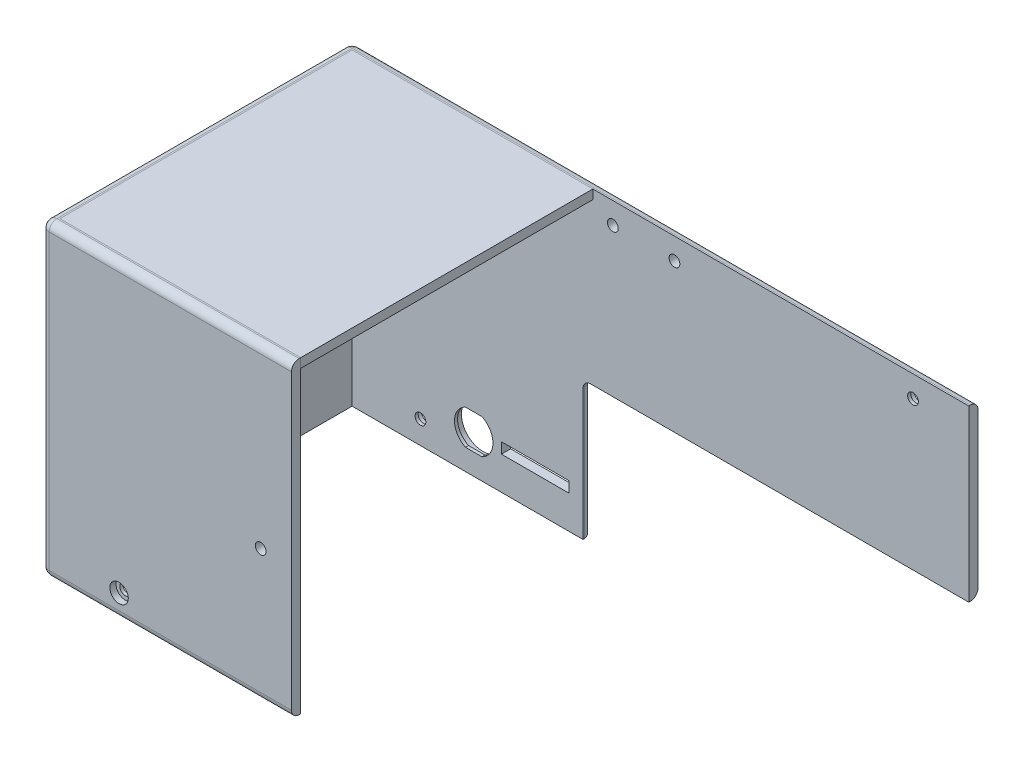
SolidWorks part; units mm, degrees
ref_plane "Front Plane" through (0, 0, 0) normal (0, 0, 1) x (1, 0, 0)
ref_plane "Top Plane" through (0, 0, 0) normal (0, 1, 0) x (1, 0, 0)
ref_plane "Right Plane" through (0, 0, 0) normal (1, 0, 0) x (0, 0, -1)
sketch "Sketch1" plane through (0, 0, 0) normal (0, 1, 0) x (1, 0, 0)
  line L0 (0, 0) -> (203.3, 0)
  line L1 (203.3, 0) -> (203.3, -3)
  line L2 (203.3, -3) -> (3, -3)
  line L5 (0, -100.9) -> (0, 0)
  line L9 (81.2, -100.9) -> (81.2, -97.9)
  line L11 (81.2, -97.9) -> (3, -97.9)
  line L12 (3, -97.9) -> (3, -3)
  line L13 (0, -100.9) -> (81.2, -100.9)
  dimension "D1" = 200.3
  dimension "D2" = 3
  dimension "D3" = 81.2
  dimension "D4" = 3
  dimension "D5" = 100.9
  dimension "D6" = 3
extrude "Main_Body" add sketch "Sketch1" along normal blind 100.2
sketch "Sketch3" plane through (0, 0, 0) normal (-1, 0, 0) x (0, 0, 1)
  line L0 (0, 0) -> (100.9, 0) construction
  line L1 (0, 100.2) -> (0, 0) construction
  line L2 (17.5, 7.5) -> (83.4, 7.5) construction
  line L3 (100.9, 100.2) -> (100.9, 0) construction
  circle A0 centre (83.4, 7.5) radius 1.75
  circle A1 centre (17.5, 7.5) radius 1.75
  dimension "D1" = 3.5
  dimension "D3" = 3.5
  dimension "D2" = 7.5
  dimension "D4" = 17.5
  dimension "D5" = 17.5
extrude "Left_Screw_Holes" [suppressed] cut sketch "Sketch3" against normal blind 10
sketch "Sketch4" [suppressed] plane through (0, 0, 0) normal (-1, 0, 0) x (0, 0, 1)
  circle A0 centre (17.5, 7.5) radius 3
  circle A1 centre (83.4, 7.5) radius 3
  dimension "D1" = 6
  dimension "D2" = 6
extrude "Left_Screw_Heads" [suppressed] cut sketch "Sketch4" against normal blind 2
sketch "Sketch5" plane through (0, 0, 0) normal (0, 0, -1) x (-1, 0, 0)
  line L0 (0, 100.2) -> (0, 0) construction
  line L1 (-203.3, 0) -> (0, 0) construction
  line L2 (-25.2, 7.5) -> (-185.2, 7.5) construction
  line L3 (-185.2, 7.5) -> (-185.2, 93.2) construction
  line L4 (-185.2, 93.2) -> (-185.2, 100.2) construction
  line L5 (-203.3, 100.2) -> (0, 100.2) construction
  circle A0 centre (-25.2, 7.5) radius 1.75
  circle A1 centre (-185.2, 7.5) radius 1.75
  circle A2 centre (-185.2, 93.2) radius 1.75
  dimension "D1" = 3.5
  dimension "D2" = 25.2
  dimension "D3" = 7.5
  dimension "D5" = 3.5
  dimension "D6" = 3.5
  dimension "D4" = 160
  dimension "D7" = 7
extrude "Back_Screw_Holes" cut sketch "Sketch5" against normal blind 10
sketch "Sketch12" plane through (0, 0, 0) normal (0, 0, -1) x (-1, 0, 0)
  circle A0 centre (-25.2, 7.5) radius 3
  circle A1 centre (-185.2, 7.5) radius 3
  circle A2 centre (-185.2, 93.2) radius 3
  dimension "D1" = 6
  dimension "D2" = 6
  dimension "D3" = 6
extrude "Back_Screw_Heads" cut sketch "Sketch12" against normal blind 2
sketch "Sketch6" plane through (0, 0, 3) normal (0, 0, 1) x (1, 0, 0)
  line L1 (78, 45) -> (298, 45)
  line L2 (78, 45) -> (78, 0)
  line L3 (78, 0) -> (298, 0)
  line L4 (298, 45) -> (298, 0)
  line L5 (3, 0) -> (203.3, 0) construction
  line L6 (0, 100.2) -> (0, 0) construction
  dimension "D1" = 45
  dimension "D2" = 220
  dimension "D4" = 78
extrude "Paper_Through_Hole" cut sketch "Sketch6" against normal blind 10
sketch "Sketch7" plane through (0, 0, 100.9) normal (0, 0, 1) x (1, 0, 0)
  line L0 (0, 0) -> (81.2, 0) construction
  line L1 (0, 100.2) -> (0, 0) construction
  circle A0 centre (25.2, 7.5) radius 1.75
  dimension "D1" = 3.5
  dimension "D2" = 7.5
  dimension "D3" = 25.2
extrude "Front_Left_Screw_Hole" cut sketch "Sketch7" against normal blind 10
sketch "Sketch8" plane through (0, 0, 100.9) normal (0, 0, 1) x (1, 0, 0)
  circle A0 centre (25.2, 7.5) radius 3
  dimension "D1" = 6
extrude "Front_Left_Screw_Head" cut sketch "Sketch8" against normal blind 2
sketch "Sketch9" plane through (0, 100.2, 0) normal (0, 1, 0) x (1, 0, 0)
  line L1 (81.2, -97.9) -> (3, -97.9)
  line L2 (81.2, -97.9) -> (81.2, -3)
  line L3 (81.2, -3) -> (3, -3)
  line L4 (3, -97.9) -> (3, -3)
extrude "Boss-Extrude1" add sketch "Sketch9" against normal blind 3 separate body
sketch "Sketch10" plane through (0, 0, 0) normal (0, 0, -1) x (-1, 0, 0)
  line L0 (-107.7, 93.2) -> (-87.7, 93.2) construction
  line L1 (-203.3, 100.2) -> (0, 100.2) construction
  line L2 (0, 93.2) -> (-87.7, 93.2) construction
  line L3 (0, 100.2) -> (0, 0) construction
  circle A0 centre (-107.7, 93.2) radius 1.75
  circle A1 centre (-87.7, 93.2) radius 1.75
  dimension "D1" = 20
  dimension "D3" = 3.5
  dimension "D4" = 3.5
  dimension "D2" = 7
  dimension "D5" = 87.7
extrude "Hinge_Holes" cut sketch "Sketch10" against normal blind 10
sketch "Sketch11" plane through (0, 0, 100.9) normal (0, 0, 1) x (1, 0, 0)
  line L0 (0, 0) -> (81.2, 0) construction
  line L1 (81.2, 100.2) -> (81.2, 0) construction
  circle A0 centre (71.2, 43) radius 1.75
  dimension "D1" = 43
  dimension "D3" = 3.5
  dimension "D2" = 10
extrude "Latch_Hole" cut sketch "Sketch11" against normal blind 10
fillet "Fillet3" radius 2.5 11 edges at (101.65, 100.2, 0) (0, 100.2, 50.45) (0, 50.1, 0) (0, 50.1, 100.9) (40.6, 0, 100.9) (39, 0, 0) (0, 0, 50.45) (40.6, 100.2, 100.9) (140.65, 45, 0) (78, 45, 1.5) (78, 22.5, 0)
sketch "Sketch13" plane through (0, 0, 0) normal (0, 0, -1) x (-1, 0, 0)
  line L0 (-75.5, 2.5) -> (-2.5, 2.5) construction
  line L1 (-2.5, 2.5) -> (-2.5, 97.7) construction
  circle A0 centre (-42.5, 12.5) radius 7
  dimension "D1" = 14
  dimension "D2" = 10
  dimension "D3" = 40
extrude "Cut-Extrude1" cut sketch "Sketch13" against normal blind 2
sketch "Sketch14" plane through (0, 0, 2) normal (0, 0, -1) x (-1, 0, 0)
  line L0 (-45.1721, 18.15) -> (-39.8279, 18.15)
  line L1 (-39.8279, 6.85) -> (-45.1721, 6.85)
  arc A0 (-39.8279, 18.15) -> (-39.8279, 6.85) centre (-42.5, 12.5) cw
  arc A1 (-45.1721, 6.85) -> (-45.1721, 18.15) centre (-42.5, 12.5) cw
  circle A2 centre (-42.5, 12.5) radius 7 construction
  dimension "D1" = 6.25
  dimension "D3" = 6.25
  dimension "D2" = 11.3
extrude "Cut-Extrude2" cut sketch "Sketch14" against normal up to next (1 mm away)
sketch "Sketch15" plane through (0, 0, 0) normal (0, 0, -1) x (-1, 0, 0)
  line L0 (-49.5, 12.5) -> (-51.5, 12.5) construction
  line L1 (-73.5, 14.25) -> (-51.5, 14.25)
  line L2 (-73.5, 14.25) -> (-73.5, 10.75)
  line L3 (-73.5, 10.75) -> (-51.5, 10.75)
  line L4 (-51.5, 14.25) -> (-51.5, 10.75)
  line L5 (-73.5, 12.5) -> (-75.5, 12.5) construction
  line L6 (-75.5, 42.5) -> (-75.5, 2.5) construction
  circle A0 centre (-42.5, 12.5) radius 7 construction
  circle A1 centre (-42.5, 12.5) radius 7 construction
  point P12 (-51.5, 12.5)
  dimension "D1" = 3.5
  dimension "D2" = 22
extrude "Cut-Extrude3" cut sketch "Sketch15" against normal up to next (3 mm away)
